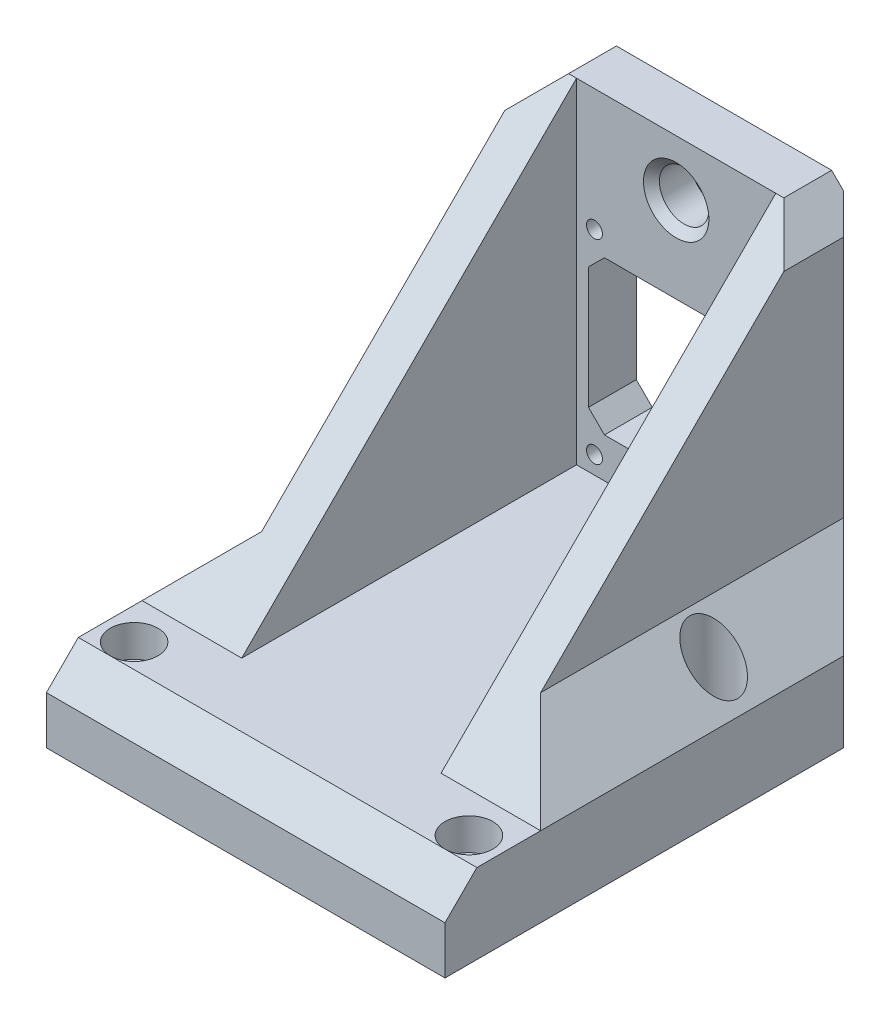
SolidWorks part; units mm, degrees
ref_plane "Front Plane" through (0, 0, 0) normal (0, 0, 1) x (1, 0, 0)
ref_plane "Top Plane" through (0, 0, 0) normal (0, 1, 0) x (1, 0, 0)
ref_plane "Right Plane" through (0, 0, 0) normal (1, 0, 0) x (0, 0, -1)
sketch "Sketch1" plane through (0, 0, 0) normal (0, 1, 0) x (1, 0, 0)
  line L1 (-25, 30) -> (25, 30)
  line L2 (-25, 30) -> (-25, -30)
  line L3 (-25, -30) -> (25, -30)
  line L4 (25, 30) -> (25, -30)
  line L5 (-25, 30) -> (25, -30) construction
  line L6 (-25, -30) -> (25, 30) construction
  point P0 (0, 0)
  dimension "D1" = 50
  dimension "D2" = 60
extrude "Boss-Extrude1" add sketch "Sketch1" along normal blind 10
sketch "Sketch2" plane through (0, 0, 0) normal (0, 1, 0) x (1, 0, 0)
  line L0 (-25, -30) -> (25, -30) construction
  line L1 (-21, -23) -> (21, -23) construction
  line L2 (-21, -23) -> (-21, 7.7) construction
  line L3 (-21, 7.7) -> (21, 7.7) construction
  line L4 (21, -23) -> (21, 7.7) construction
  line L5 (-21, -23) -> (21, 7.7) construction
  line L6 (-21, 7.7) -> (21, -23) construction
  circle A0 centre (-21, 7.7) radius 1.5
  circle A1 centre (-21, -23) radius 1.5
  circle A2 centre (21, 7.7) radius 1.5
  circle A3 centre (21, -23) radius 1.5
  point P0 (0, -7.65)
  dimension "D4" = 3
  dimension "D1" = 42
  dimension "D2" = 30.7
  dimension "D3" = 7
extrude "Cut-Extrude1" cut sketch "Sketch2" along normal blind 6
sketch "Sketch3" plane through (0, 6, 0) normal (0, -1, 0) x (1, 0, 0)
  circle A0 centre (-21, 23) radius 3
  circle A1 centre (21, 23) radius 3
  circle A2 centre (21, -7.7) radius 3
  circle A3 centre (-21, -7.7) radius 3
  dimension "D1" = 6
extrude "Cut-Extrude2" cut sketch "Sketch3" against normal up to next
sketch "Sketch5" plane through (0, 10, 0) normal (0, 1, 0) x (1, 0, 0)
  line L0 (25, 30) -> (-25, 30) construction
  line L1 (-12.5, 24) -> (12.5, 24)
  line L2 (-12.5, 24) -> (-12.5, 30)
  line L3 (-12.5, 30) -> (12.5, 30)
  line L4 (12.5, 24) -> (12.5, 30)
  line L5 (-12.5, 24) -> (12.5, 30) construction
  line L6 (-12.5, 30) -> (12.5, 24) construction
  point P0 (0, 27)
  dimension "D1" = 6
  dimension "D2" = 25
extrude "Boss-Extrude3" add sketch "Sketch5" along normal blind 42
sketch "Sketch6" plane through (0, 0, -30) normal (0, 0, -1) x (-1, 0, 0)
  line L0 (-25, 10) -> (-12.5, 10) construction
  line L1 (-11, 15) -> (11, 15)
  line L2 (-11, 15) -> (-11, 34.25)
  line L3 (-11, 34.25) -> (11, 34.25)
  line L4 (11, 15) -> (11, 34.25)
  line L5 (-11, 15) -> (11, 34.25) construction
  line L6 (-11, 34.25) -> (11, 15) construction
  point P0 (0, 24.625)
  dimension "D1" = 22
  dimension "D2" = 19.25
  dimension "D3" = 5
extrude "Cut-Extrude3" cut sketch "Sketch6" against normal up to next
sketch "Sketch7" plane through (0, 0, -24) normal (0, 0, 1) x (1, 0, 0)
  line L0 (-12.5, 10) -> (12.5, 10) construction
  line L1 (-10.25, 12.25) -> (10.25, 12.25) construction
  line L2 (-10.25, 12.25) -> (-10.25, 36.7) construction
  line L3 (-10.25, 36.7) -> (10.25, 36.7) construction
  line L4 (10.25, 12.25) -> (10.25, 36.7) construction
  line L5 (-10.25, 12.25) -> (10.25, 36.7) construction
  line L6 (-10.25, 36.7) -> (10.25, 12.25) construction
  circle A0 centre (10.25, 12.25) radius 1
  circle A1 centre (-10.25, 12.25) radius 1
  circle A2 centre (-10.25, 36.7) radius 1
  circle A3 centre (10.25, 36.7) radius 1
  point P0 (0, 24.475)
  dimension "D4" = 2
  dimension "D1" = 20.5
  dimension "D2" = 24.45
  dimension "D3" = 2.25
extrude "Cut-Extrude4" cut sketch "Sketch7" against normal blind 2.5
sketch "Sketch8" plane through (0, 0, -26.5) normal (0, 0, 1) x (1, 0, 0)
  circle A0 centre (-10.25, 36.7) radius 2
  circle A1 centre (10.25, 36.7) radius 2
  circle A2 centre (10.25, 12.25) radius 2
  circle A3 centre (-10.25, 12.25) radius 2
  dimension "D1" = 4
extrude "Cut-Extrude5" cut sketch "Sketch8" against normal up to next
sketch "Sketch9" plane through (12.5, 0, 0) normal (1, 0, 0) x (0, 0, -1)
  line L0 (30, 52) -> (24, 52)
  line L4 (-18, 10) -> (30, 10)
  line L5 (30, 10) -> (30, 52)
  line L6 (30, 52) -> (30, 10) construction
  line L8 (-18, 10) -> (24, 52)
  point P4 (-6, 10.4458)
  dimension "D1" = 45
extrude "Boss-Extrude4" add sketch "Sketch9" along normal blind 5
mirror "Mirror1" about plane through (0, 0, 0) normal (1, 0, 0) of "Boss-Extrude4"
chamfer "Chamfer1" distance 7.5 angle 45 2 edges at (17.5, 10, -6) (-17.5, 10, -6)
chamfer "Chamfer2" distance 10 angle 45 2 edges at (-25, 5, -30) (25, 5, -30)
chamfer "Chamfer4" distance 6.5 angle 45 1 edges at (0, 0, -30)
chamfer "Chamfer5" distance 4 angle 45 2 edges at (17.5, 52, -25.75) (-17.5, 52, -25.75)
chamfer "Chamfer6" distance 4 angle 45 1 edges at (0, 10, 30)
chamfer "Chamfer7" distance 2 angle 45 4 edges at (-11, 34.25, -27) (-11, 15, -27) (11, 15, -27) (11, 34.25, -27)
sketch "Sketch10" plane through (0, 0, -30) normal (0, 0, -1) x (-1, 0, 0)
  circle A0 centre (0, 45) radius 3.1
  circle A1 centre (-10.25, 36.7) radius 2 construction
  point P4 (0, 0)
  dimension "D1" = 6.2
  dimension "D2" = 8.3
extrude "Cut-Extrude6" cut sketch "Sketch10" against normal up to next
chamfer "Chamfer8" distance 1 angle 45 2 edges at (-3.1, 45, -24) (-3.1, 45, -30)
